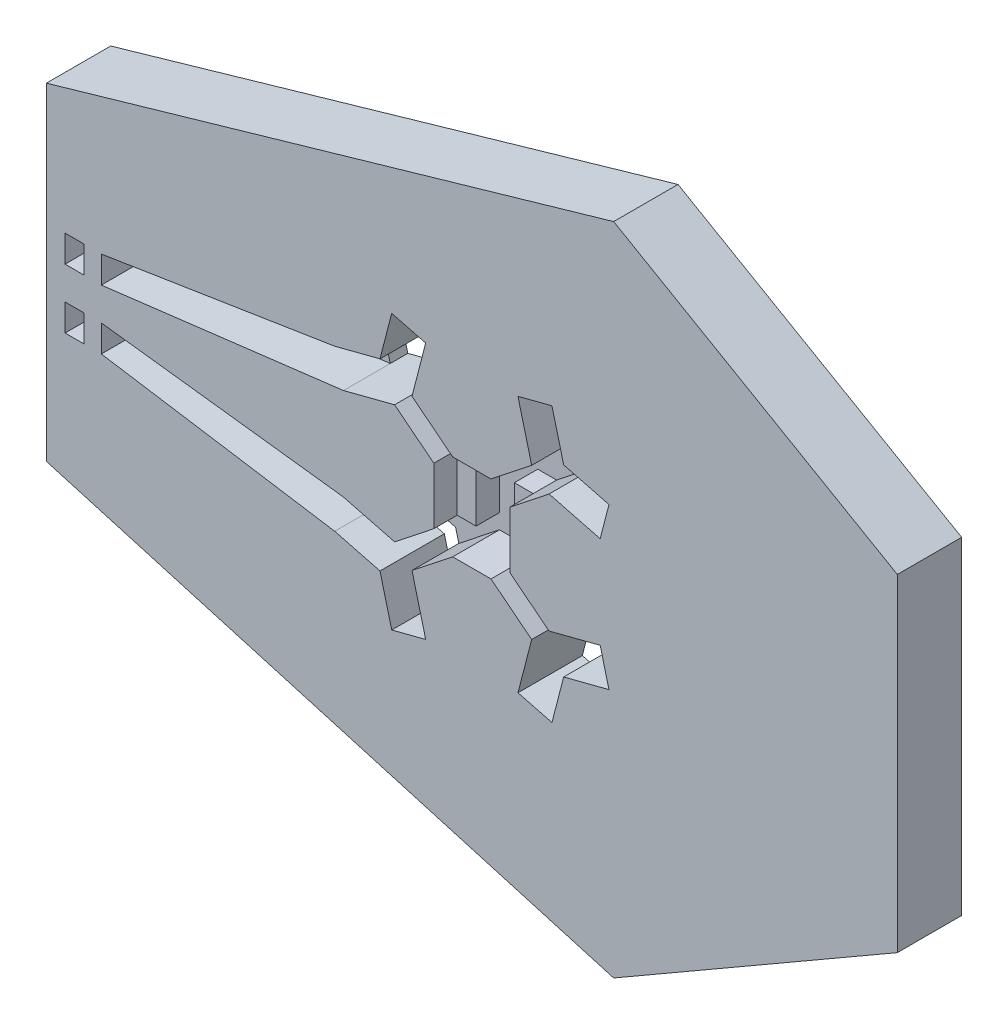
SolidWorks part; units mm, degrees
note: The reader was unsure of these and kept them because the rebuilt part matched: shared geometry of "Sketch1<3>".
ref_plane "Front Plane" through (0, 0, 0) normal (0, 0, 1) x (1, 0, 0)
ref_plane "Top Plane" through (0, 0, 0) normal (0, 1, 0) x (1, 0, 0)
ref_plane "Right Plane" through (0, 0, 0) normal (1, 0, 0) x (0, 0, -1)
sketch "Sketch1" plane through (0, 0, 0) normal (0, 0, 1) x (1, 0, 0)
  line L42 (-6.4, 3.7) -> (-3.9, 3.7) construction
  line L43 (-6.4, 3.7) -> (-8.4, 3.7) construction
  line L49 (-6.4, -3.7) -> (-3.9, -3.7) construction
  line L50 (-8.4, -3.7) -> (-6.4, -3.7) construction
  line L51 (-8.4, -3.7) -> (-8.4, 3.7) construction
  line L52 (-8.4, -3.7) -> (-1.9, -3.7) construction
  line L53 (-1.9, -3.7) -> (-1.9, 3.7) construction
  line L54 (-8.4, 3.7) -> (-1.9, 3.7) construction
  line L55 (-8.4, 3.7) -> (-8.4, -3.7) construction
  line L62 (6.9744, -28) -> (31.2231, -14) construction
  line L63 (31.2231, -14) -> (31.2231, 14) construction
  line L64 (31.2231, 14) -> (6.9744, 28) construction
  line L65 (-41.5231, 14) -> (6.9744, 28) construction
  line L66 (-41.5231, 14) -> (-41.5231, -14) construction
  line L67 (6.9744, -28) -> (-41.5231, -14) construction
  line L68 (-39.9231, -1.4) -> (-38.3231, -1.4) construction
  line L69 (-38.3231, -1.4) -> (-38.3231, 1.4) construction
  line L70 (-39.9231, 1.4) -> (-38.3231, 1.4) construction
  line L71 (-39.9231, -1.4) -> (-39.9231, 1.4) construction
  line L72 (-39.9231, -3.7) -> (-38.3231, -3.7) construction
  line L73 (-38.3231, -3.7) -> (-38.3231, 3.7) construction
  line L74 (-39.9231, 3.7) -> (-38.3231, 3.7) construction
  line L75 (-39.9231, -3.7) -> (-39.9231, 3.7) construction
  line L82 (-6.4, 3.7) -> (-3.9, 3.7)
  line L83 (-6.4, 3.7) -> (-8.4, 3.7)
  line L89 (-6.4, -3.7) -> (-3.9, -3.7)
  line L90 (-8.4, -3.7) -> (-6.4, -3.7)
  line L91 (-8.4, -3.7) -> (-8.4, 3.7)
  line L92 (-8.4, -3.7) -> (-1.9, -3.7)
  line L93 (-1.9, -3.7) -> (-1.9, 3.7)
  line L94 (-8.4, 3.7) -> (-1.9, 3.7)
  line L95 (-8.4, 3.7) -> (-8.4, -3.7)
  line L102 (6.9744, -28) -> (31.2231, -14)
  line L103 (31.2231, -14) -> (31.2231, 14)
  line L104 (31.2231, 14) -> (6.9744, 28)
  line L105 (-41.5231, 14) -> (6.9744, 28)
  line L106 (-41.5231, 14) -> (-41.5231, -14)
  line L107 (6.9744, -28) -> (-41.5231, -14)
  line L108 (-39.9231, -1.4) -> (-38.3231, -1.4)
  line L109 (-38.3231, -1.4) -> (-38.3231, 1.4)
  line L110 (-39.9231, 1.4) -> (-38.3231, 1.4)
  line L111 (-39.9231, -1.4) -> (-39.9231, 1.4)
  line L112 (-39.9231, -3.7) -> (-38.3231, -3.7)
  line L113 (-38.3231, -3.7) -> (-38.3231, 3.7)
  line L114 (-39.9231, 3.7) -> (-38.3231, 3.7)
  line L115 (-39.9231, -3.7) -> (-39.9231, 3.7)
extrude "Boss-Extrude1" add sketch "Sketch1" along normal blind 1.5
extrude "Boss-Extrude2" add sketch "Sketch1<3>" along normal blind 4 from surface
sketch "Sketch1<3>" plane through (0, 0, 0) normal (0, 0, 1) x (1, 0, 0) same geometry as "Sketch1"
ref_plane "Plane1" through (0, 0, 0) normal (0, -1, 0) x (-1, 0, 0)
ref_plane "Plane2" through (-5.15, 0, 0) normal (1, 0, 0) x (0, 0, -1)
sketch "WireCutExtrude" plane through (0, 0, 5.5) normal (0, 0, 1) x (1, 0, 0)
  line L0 (-9.0949, 10.9725) -> (-10.5382, 5.3882)
  line L1 (-10.5382, 5.3882) -> (-16.1225, 3.9449)
  line L2 (-11.9995, 11.7232) -> (-13.0004, 7.8504)
  line L3 (-13.0004, 7.8504) -> (-16.8732, 6.8495)
  line L4 (-16.8732, 6.8495) -> (-16.1225, 3.9449)
  line L5 (-11.9995, 11.7232) -> (-9.0949, 10.9725)
  line L6 (-9.4207, 4.2707) -> (-13.0004, 7.8504) construction
  line L14 (-2.9716, -11.813) -> (-1.1403, -4.7276)
  line L15 (-0.4224, -4.0097) -> (6.663, -2.1784)
  line L16 (6.663, 2.1784) -> (-0.4224, 4.0097)
  line L17 (-1.1403, 4.7276) -> (-2.9716, 11.813)
  line L18 (-7.3284, 11.813) -> (-9.1597, 4.7276)
  line L19 (-9.8776, 4.0097) -> (-16.963, 2.1784)
  line L20 (-16.963, -2.1784) -> (-9.8776, -4.0097)
  line L21 (-9.1597, -4.7276) -> (-7.3284, -11.813)
  line L22 (-2.9716, -11.813) -> (-1.1403, -4.7276) construction
  line L23 (-0.4224, -4.0097) -> (6.663, -2.1784) construction
  line L24 (6.663, 2.1784) -> (-0.4224, 4.0097) construction
  line L25 (-1.1403, 4.7276) -> (-2.9716, 11.813) construction
  line L26 (-7.3284, 11.813) -> (-9.1597, 4.7276) construction
  line L27 (-9.8776, 4.0097) -> (-16.963, 2.1784) construction
  line L28 (-16.963, -2.1784) -> (-9.8776, -4.0097) construction
  line L29 (-9.1597, -4.7276) -> (-7.3284, -11.813) construction
  arc A9 (-0.4224, -4.0097) -> (-1.1403, -4.7276) centre (-0.1722, -4.9778) ccw
  arc A10 (6.663, -2.1784) -> (6.663, 2.1784) centre (6.1, 0) ccw
  arc A11 (-1.1403, 4.7276) -> (-0.4224, 4.0097) centre (-0.1722, 4.9778) ccw
  arc A12 (-2.9716, 11.813) -> (-7.3284, 11.813) centre (-5.15, 11.25) ccw
  arc A13 (-9.8776, 4.0097) -> (-9.1597, 4.7276) centre (-10.1278, 4.9778) ccw
  arc A14 (-16.963, 2.1784) -> (-16.963, -2.1784) centre (-16.4, 0) ccw
  arc A15 (-9.1597, -4.7276) -> (-9.8776, -4.0097) centre (-10.1278, -4.9778) ccw
  arc A16 (-7.3284, -11.813) -> (-2.9716, -11.813) centre (-5.15, -11.25) ccw
  arc A17 (-0.4224, -4.0097) -> (-1.1403, -4.7276) centre (-0.1722, -4.9778) ccw construction
  arc A18 (6.663, -2.1784) -> (6.663, 2.1784) centre (6.1, 0) ccw construction
  arc A19 (-1.1403, 4.7276) -> (-0.4224, 4.0097) centre (-0.1722, 4.9778) ccw construction
  arc A20 (-2.9716, 11.813) -> (-7.3284, 11.813) centre (-5.15, 11.25) ccw construction
  arc A21 (-9.8776, 4.0097) -> (-9.1597, 4.7276) centre (-10.1278, 4.9778) ccw construction
  arc A22 (-16.963, 2.1784) -> (-16.963, -2.1784) centre (-16.4, 0) ccw construction
  arc A23 (-9.1597, -4.7276) -> (-9.8776, -4.0097) centre (-10.1278, -4.9778) ccw construction
  arc A24 (-7.3284, -11.813) -> (-2.9716, -11.813) centre (-5.15, -11.25) ccw construction
  dimension "D2" = 3
  dimension "D3" = 4
  dimension "D4" = 1.5
  dimension "D1" = 0
extrude "Cut-Extrude1" cut sketch "WireCutExtrude" against normal up to surface (5.5 mm away) up to face at (-1.1085, 0, 0)
mirror "Mirror1" about plane through (0, 0, 0) normal (0, -1, 0) of "Cut-Extrude1"
mirror "Mirror2" about plane through (-5.15, 0, 0) normal (1, 0, 0) of "Mirror1", "Cut-Extrude1"
sketch "Sketch5" plane through (0, 0, 5.5) normal (0, 0, 1) x (1, 0, 0)
  line L0 (-10.5382, 5.3882) -> (-8.4, 3.7) construction
  line L1 (-10.2647, 6.4464) -> (-6.7863, 3.7)
  line L2 (-8.4, 3.7) -> (-1.9, 3.7) construction
  line L3 (-8.4, 2.4259) -> (-11.754, 5.074)
  line L4 (-8.4, -3.7) -> (-8.4, 3.7) construction
  line L5 (-8.4, 3.7) -> (-9.0197, 2.9151) construction
  line L6 (-10.5382, 5.3882) -> (-16.1225, 3.9449) construction
  line L7 (-8.4, 3.7) -> (-7.7803, 4.4849) construction
  line L8 (-9.0949, 10.9725) -> (-10.5382, 5.3882) construction
  line L9 (-1.9, 3.7) -> (0.2382, 5.3882) construction
  line L10 (-3.5137, 3.7) -> (-0.0353, 6.4464)
  line L11 (0.2382, 5.3882) -> (-1.2051, 10.9725) construction
  line L12 (-1.9, 2.4259) -> (1.454, 5.074)
  line L13 (-1.9, -3.7) -> (-1.9, 3.7) construction
  line L14 (-39.9231, 1.4) -> (-38.3231, 1.4) construction
  line L15 (-38.3231, 1.4) -> (-38.3231, 3.7) construction
  line L16 (-38.3231, 3.7) -> (-39.9231, 3.7) construction
  line L17 (-39.9231, 3.7) -> (-39.9231, 1.4) construction
  line L18 (5.8225, 3.9449) -> (0.2382, 5.3882) construction
  line L19 (-2.5197, 4.4849) -> (-1.9, 3.7) construction
  line L20 (-1.9, 3.7) -> (-1.2803, 2.9151) construction
  line L21 (-11.754, 5.074) -> (-10.5382, 5.3882)
  line L22 (-39.9231, 1.4) -> (-38.3231, 1.4) construction
  line L23 (-38.3231, 1.4) -> (-38.3231, 3.7) construction
  line L24 (-38.3231, 3.7) -> (-39.9231, 3.7) construction
  line L25 (-39.9231, 3.7) -> (-39.9231, 1.4) construction
  line L26 (-10.5382, 5.3882) -> (-10.2647, 6.4464)
  line L27 (-6.7863, 3.7) -> (-8.4, 3.7)
  line L28 (-8.4, 3.7) -> (-8.4, 2.4259)
  line L29 (-3.5137, 3.7) -> (-1.9, 3.7)
  line L30 (-36.8231, 1.4) -> (-36.8231, 3.7)
  line L31 (-1.9, 3.7) -> (-1.9, 2.4259)
  line L32 (-36.8231, 3.7) -> (-16.8732, 6.8495)
  line L33 (-16.8732, 6.8495) -> (-16.1225, 3.9449)
  line L34 (-16.1225, 3.9449) -> (-36.8231, 1.4)
  line L35 (1.454, 5.074) -> (0.2382, 5.3882)
  line L36 (0.2382, 5.3882) -> (-0.0353, 6.4464)
  dimension "D2" = 1
  dimension "D1" = 1.5
extrude "Cut-Extrude2" cut sketch "Sketch5" against normal blind 4
mirror "Mirror3" about plane through (0, 0, 0) normal (0, -1, 0) of "Cut-Extrude2"
sketch "Sketch6" plane through (0, 0, 1.5) normal (0, 0, 1) x (1, 0, 0)
  line L0 (-3.5137, 2.4259) -> (-1.9, 2.4259)
  line L1 (-1.9, 3.7) -> (-8.4, 3.7) construction
  line L2 (-1.9, 3.7) -> (-1.9, -3.7) construction
  line L3 (-1.9, -3.7) -> (-8.4, -3.7) construction
  line L4 (-8.4, 3.7) -> (-8.4, -3.7) construction
  line L5 (-8.4, 2.4259) -> (-6.7863, 2.4259)
  line L6 (-8.4, 2.4259) -> (-8.4, -2.4259)
  line L7 (-8.4, -2.4259) -> (-6.7863, -2.4259)
  line L8 (-1.9, 2.4259) -> (-1.9, -2.4259)
  line L9 (-3.5137, -2.4259) -> (-1.9, -2.4259)
  line L10 (-6.7863, 2.4259) -> (-6.7863, -2.4259)
  line L12 (-3.5137, 2.4259) -> (-3.5137, -2.4259)
extrude "Boss-Extrude3" add sketch "Sketch6" along normal blind 2
